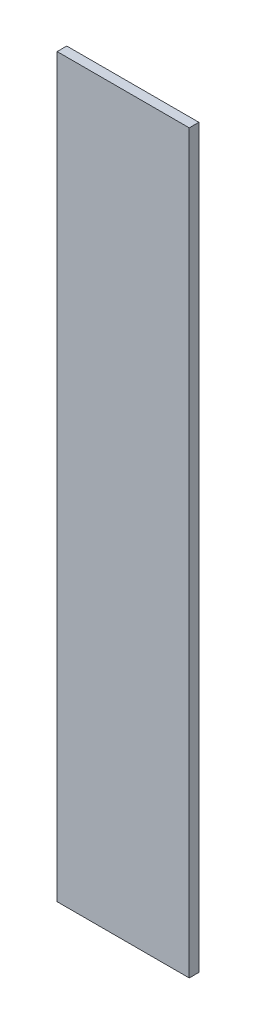
SolidWorks part; units mm, degrees
material "Beech"
ref_plane "Front" through (0, 0, 0) normal (0, 0, 1) x (1, 0, 0)
ref_plane "Top" through (0, 0, 0) normal (0, 1, 0) x (1, 0, 0)
ref_plane "Right" through (0, 0, 0) normal (1, 0, 0) x (0, 0, -1)
ref_axis "side-side" through (80.9, 0, 0) along (-1, 0, 0)
ref_axis "up-down" through (0, 50, 0) along (0, -1, 0)
ref_axis "front-back" through (0, 0, -80.9) along (0, 0, 1)
sketch "Sketch1" plane through (0, 0, 0) normal (0, 0, 1) x (1, 0, 0)
  line L1 (-34, 394.9595) -> (34, 394.9595)
  line L2 (-34, 394.9595) -> (-34, 16)
  line L3 (-34, 16) -> (34, 16)
  line L4 (34, 394.9595) -> (34, 16)
  point P5 (0, 16)
  dimension "D1" = 16
  dimension "D2" = 68
  dimension "D3" = 378.9595
extrude "Boss-Extrude1" add sketch "Sketch1" along normal blind 4.953
